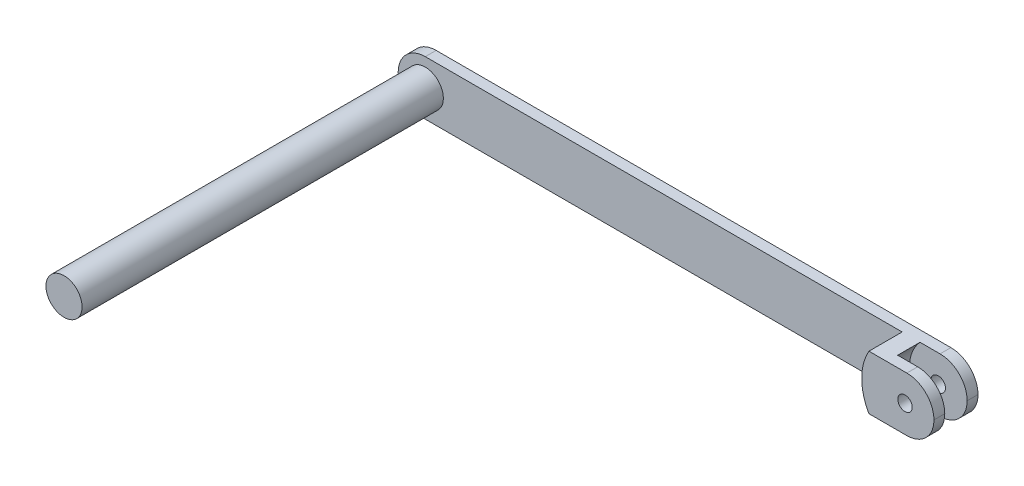
SolidWorks part; units mm, degrees
material "PBT General Purpose"
ref_plane "Front Plane" through (0, 0, 0) normal (0, 0, 1) x (1, 0, 0)
ref_plane "Top Plane" through (0, 0, 0) normal (0, 1, 0) x (1, 0, 0)
ref_plane "Right Plane" through (0, 0, 0) normal (1, 0, 0) x (0, 0, -1)
sketch "Sketch1" plane through (0, 0, 0) normal (0, 0, 1) x (1, 0, 0)
  line L0 (0, 7.5) -> (150, 7.5)
  line L6 (0, -7.5) -> (150, -7.5)
  line L7 (150, 7.5) -> (150, -7.5)
  arc A2 (0, 7.5) -> (0, -7.5) centre (0, 0) ccw
  dimension "D1" = 15
  dimension "D2" = 150
extrude "Boss-Extrude1" add sketch "Sketch1" along normal blind 3
sketch "Sketch2" plane through (0, 0, 3) normal (0, 0, 1) x (1, 0, 0)
  circle A0 centre (0, 0) radius 5
  dimension "D1" = 10
extrude "Boss-Extrude2" add sketch "Sketch2" along normal blind 8
sketch "Sketch3" plane through (0, 0, 11) normal (0, 0, 1) x (1, 0, 0)
  circle A0 centre (0, 0) radius 5 construction
  circle A1 centre (0, 0) radius 5
extrude "Boss-Extrude3" add sketch "Sketch3" along normal blind 92
sketch "Sketch7" plane through (0, 0, 3) normal (0, 0, 1) x (1, 0, 0)
  line L0 (150, 7.5) -> (0, 7.5) construction
  line L1 (150, -7.5) -> (150, 7.5) construction
  line L2 (136.9533, 7.5) -> (132.0096, 7.5)
  line L3 (0, -7.5) -> (150, -7.5) construction
  line L4 (132.0096, -7.5) -> (136.9533, -7.5)
  arc A0 (132.0096, 7.5) -> (132.0096, -7.5) centre (145, 0) ccw
  arc A1 (136.9533, 7.5) -> (136.9533, -7.5) centre (145, 0) ccw
  dimension "D1" = 30
  dimension "D2" = 22
  dimension "D3" = 7.5
  dimension "D4" = 5
extrude "Boss-Extrude6" add sketch "Sketch7" along normal blind 9.2
sketch "Sketch8" plane through (150, 0, 0) normal (1, 0, 0) x (0, 0, -1)
  line L0 (-12.2, 7.5) -> (-3, 7.5) construction
  line L1 (-12.2, -7.5) -> (-9.2, -7.5)
  line L2 (-12.2, -7.5) -> (-12.2, 7.5)
  line L3 (-12.2, 7.5) -> (-9.2, 7.5)
  line L4 (-9.2, -7.5) -> (-9.2, 7.5)
  dimension "D1" = 3
extrude "Boss-Extrude7" add sketch "Sketch8" against normal up to surface (17.9904 mm away) up to face at (131.0048, 0, 7.6)
sketch "Sketch9" plane through (0, 0, 12.2) normal (0, 0, 1) x (1, 0, 0)
  line L0 (150, 7.5) -> (132.0096, 7.5) construction
  line L1 (150, 7.5) -> (150, -7.5) construction
  circle A0 centre (142, 0) radius 2
  dimension "D1" = 4
  dimension "D2" = 7.5
  dimension "D3" = 8
extrude "Cut-Extrude2" cut sketch "Sketch9" against normal through all
fillet "Fillet2" radius 7.5 4 edges at (150, -7.5, 1.5) (150, -7.5, 10.7) (150, 7.5, 1.5) (150, 7.5, 10.7)
